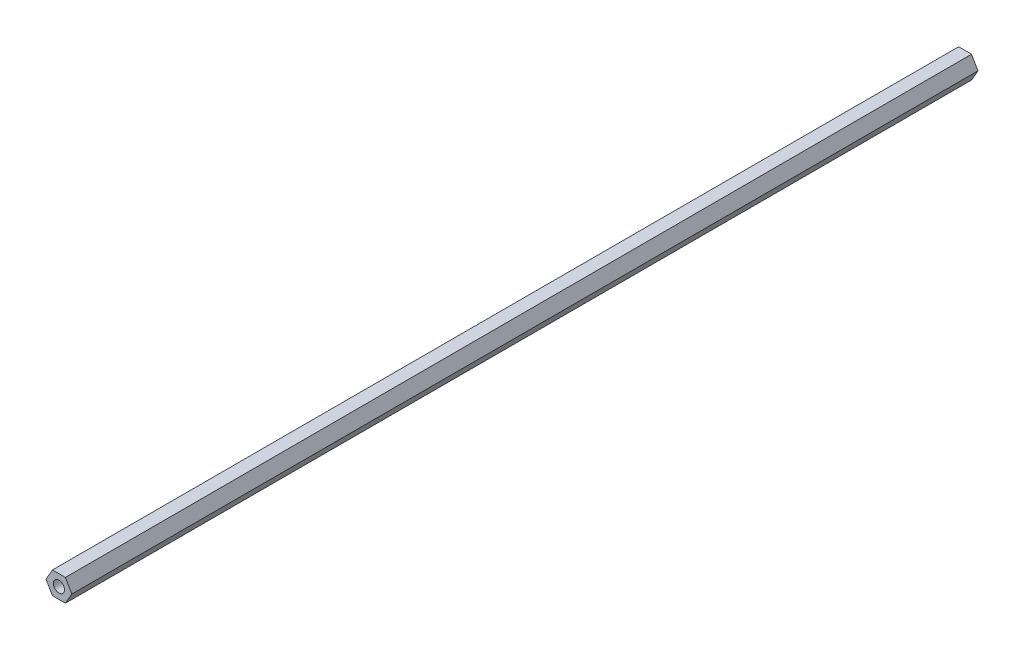
SolidWorks part; units mm, degrees
ref_plane "Front Plane" through (0, 0, 0) normal (0, 0, 1) x (1, 0, 0)
ref_plane "Top Plane" through (0, 0, 0) normal (0, 1, 0) x (1, 0, 0)
ref_plane "Right Plane" through (0, 0, 0) normal (1, 0, 0) x (0, 0, -1)
sketch "Sketch1" plane through (0, 0, 0) normal (0, 0, 1) x (1, 0, 0)
  line L0 (0, 6.35) -> (0, 0)
  line L1 (-7.3323, 0) -> (-3.6662, -6.35)
  line L2 (-3.6662, -6.35) -> (3.6662, -6.35)
  line L3 (3.6662, -6.35) -> (7.3323, 0)
  line L4 (7.3323, 0) -> (3.6662, 6.35)
  line L5 (3.6662, 6.35) -> (-3.6662, 6.35)
  line L6 (-3.6662, 6.35) -> (-7.3323, 0)
  circle A0 centre (0, 0) radius 6.35 construction
  dimension "D1" = 6.35
extrude "Boss-Extrude1" add sketch "Sketch1" along normal offset from surface (514.4834 mm away) 25.4 contours L5 L6 L1 L2 L3 L4 region at (-5.3313, 3.078, 0) offset beyond the face yes
sketch "Sketch2" plane through (0, 0, 514.4834) normal (0, 0, 1) x (1, 0, 0)
  circle A0 centre (0, 0) radius 3.175
  dimension "D1" = 6.35
extrude "Cut-Extrude1" cut sketch "Sketch2" against normal through all both and the other way through all contours A0 region at (0, 0, 514.4834)
